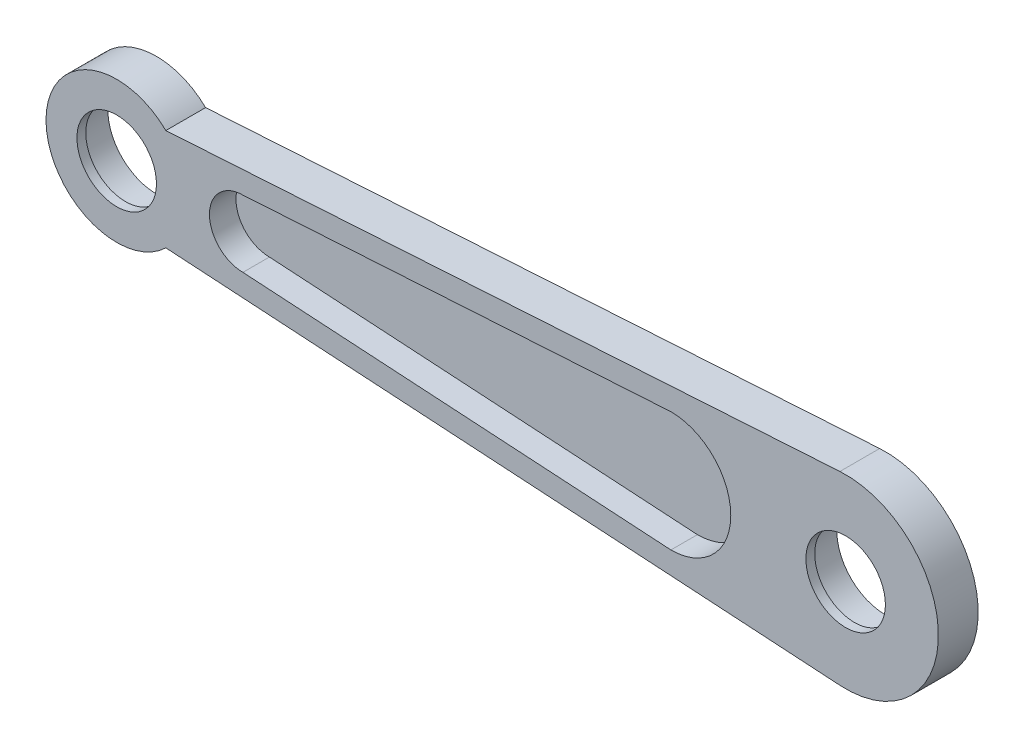
SolidWorks part; units mm, degrees
ref_plane "Front Plane" through (0, 0, 0) normal (0, 0, 1) x (1, 0, 0)
ref_plane "Top Plane" through (0, 0, 0) normal (0, 1, 0) x (1, 0, 0)
ref_plane "Right Plane" through (0, 0, 0) normal (1, 0, 0) x (0, 0, -1)
sketch "Sketch6" plane through (0, 0, 0) normal (0, 0, 1) x (1, 0, 0)
  line L0 (11.1243, -11.5) -> (163.7005, -20.9598)
  line L1 (28.5722, 7.5722) -> (125.4476, 13.5524)
  line L2 (11.1243, 11.5) -> (163.7005, 20.9598)
  line L3 (-58.5211, 0) -> (213.089, 0) construction
  line L4 (28.5722, -7.5722) -> (125.4476, -13.5524)
  circle A1 centre (165, 0) radius 11
  circle A2 centre (165, 0) radius 21
  circle A3 centre (0, 0) radius 11
  circle A4 centre (0, 0) radius 16
  circle A5 centre (165, 0) radius 9
  arc A6 (28.5722, 7.5722) -> (28.5722, -7.5722) centre (28.5722, 0) ccw
  arc A7 (125.4476, -13.5524) -> (125.4476, 13.5524) centre (125.4476, 0) ccw
  circle A8 centre (0, 0) radius 9
  point P18 (17.4629, 11.5)
  point P22 (147.3981, 11.5)
  point P23 (148.9678, 13.5636)
  point P24 (146.766, 10.4173)
  point P25 (149.121, 13.7425)
  point P26 (155.0932, 18.5163)
  dimension "D2" = 18
  dimension "D3" = 165
  dimension "D4" = 22
  dimension "D5" = 5
  dimension "D6" = 5
  dimension "D7" = 5
  dimension "D8" = 42
  dimension "D9" = 5
  dimension "D11" = 5
  dimension "D12" = 23
extrude "Boss-Extrude1" add sketch "Sketch6" along normal blind 9 contours L3 A4 L0 A2 A7 L4 A6 | L3 A6 L4 A7 | A6 L3 A7 L1 | A4 L3 A6 L1 A7 A2 L2 | A4 | A2 region at (89.6021, -12.3284, 0) region at (89.6021, 12.3284, 0) region at (85.3957, 5.3794, 0) region at (85.3957, -5.3794, 0)
extrude "Cut-Extrude1" cut sketch "Sketch6<15>" along normal through all contours A5 | A8
sketch "Sketch6<15>" plane through (0, 0, 0) normal (0, 0, 1) x (1, 0, 0) same geometry as "Sketch6"
extrude "Cut-Extrude2" cut sketch "Sketch6<17>" along normal offset from surface (7 mm away) 2 contours A1 | A3 up to face at (174, 0, 9)
sketch "Sketch6<17>" plane through (0, 0, 0) normal (0, 0, 1) x (1, 0, 0) same geometry as "Sketch6"
extrude "Cut-Extrude3" cut sketch "Sketch6<18>" against normal offset from surface (6 mm away) 3 from surface contours L1 A7 L4 A6 up to face at (176, 0, 0) starting at face at (174, 0, 9)
sketch "Sketch6<18>" plane through (0, 0, 0) normal (0, 0, 1) x (1, 0, 0) same geometry as "Sketch6"
